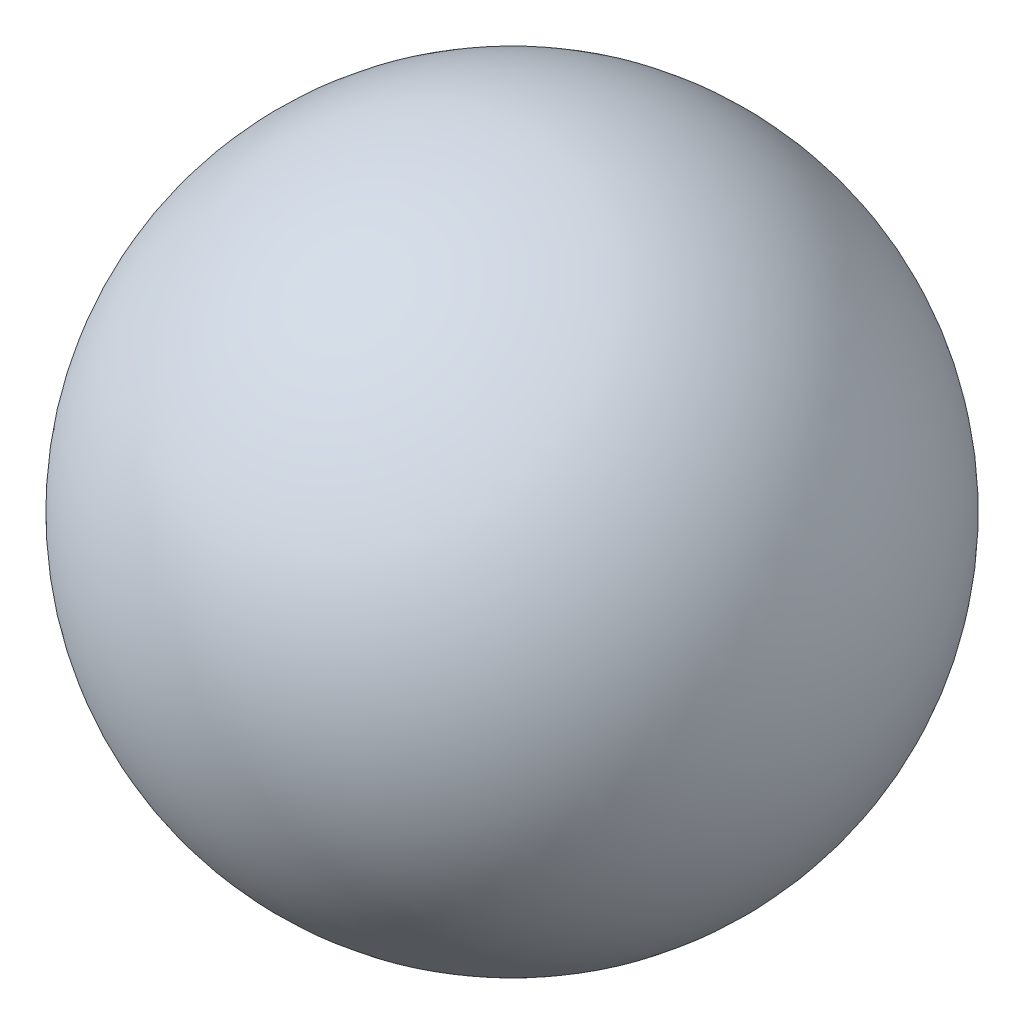
SolidWorks part; units mm, degrees
ref_plane "Front Plane" through (0, 0, 0) normal (0, 0, 1) x (1, 0, 0)
ref_plane "Top Plane" through (0, 0, 0) normal (0, 1, 0) x (1, 0, 0)
ref_plane "Right Plane" through (0, 0, 0) normal (1, 0, 0) x (0, 0, -1)
sketch "Sketch1" plane through (0, 0, 0) normal (0, 0, 1) x (1, 0, 0)
  line L0 (0, 10) -> (0, -10)
  arc A0 (0, -10) -> (0, 10) centre (0, 0) ccw
  dimension "D1" = 20
ref_axis "Axis1" through (0, -11, 0) along (0, 1, 0)
revolve "Revolve3" add sketch "Sketch1" angle 360 about L0
ref_plane "Plane1" through (0, 10, 0) normal (0, 1, 0) x (1, 0, 0)
